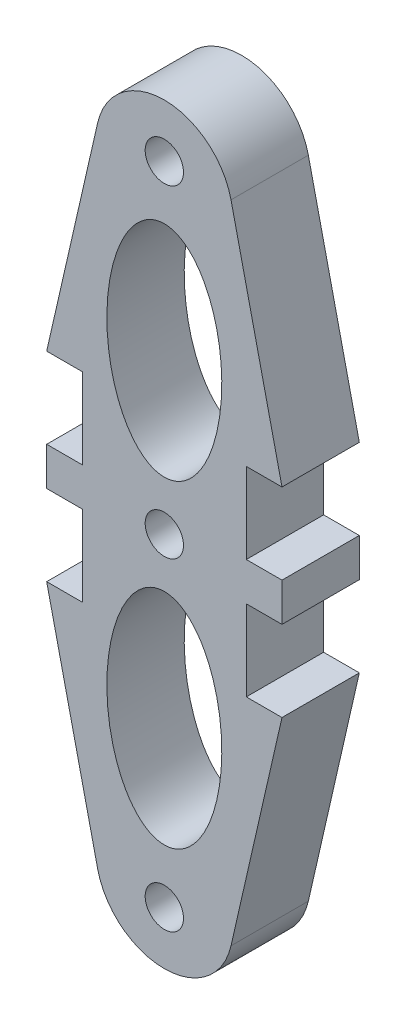
SolidWorks part; units mm, degrees
material "Acrylic (Medium-high impact)"
ref_plane "Front Plane" through (0, 0, 0) normal (0, 0, 1) x (1, 0, 0)
ref_plane "Top Plane" through (0, 0, 0) normal (0, 1, 0) x (1, 0, 0)
ref_plane "Right Plane" through (0, 0, 0) normal (1, 0, 0) x (0, 0, -1)
sketch "Sketch1" plane through (0, 0, 0) normal (0, 0, 1) x (1, 0, 0)
  line L0 (-213.0416, 464.8524) -> (49786.9584, 464.8524) construction
  line L1 (781.4592, 464.8524) -> (778.7592, 464.8524)
  line L2 (781.4592, 464.8524) -> (781.4592, 470.9524)
  line L3 (781.4592, 470.9524) -> (778.7592, 470.9524)
  line L4 (787.6592, -515.9255) -> (787.6592, 49484.0745) construction
  line L5 (-215.2216, 463.4024) -> (49784.7784, 463.4024) construction
  line L6 (793.8592, 470.9524) -> (793.8592, 487.8374) construction
  line L7 (-217.5077, 461.9524) -> (49782.4923, 461.9524) construction
  line L8 (786.2092, -537.0976) -> (786.2092, 49462.9024) construction
  line L9 (789.1092, -536.5976) -> (789.1092, 49463.4024) construction
  line L10 (793.8592, 464.8524) -> (796.5592, 464.8524)
  line L11 (781.4592, 470.9524) -> (793.8592, 470.9524) construction
  line L12 (793.8592, 470.9524) -> (796.5592, 470.9524)
  line L13 (793.8592, 464.8524) -> (793.8592, 470.9524)
  line L14 (778.7592, 464.8524) -> (778.7592, 461.9524)
  line L15 (796.5592, 464.8524) -> (796.5592, 461.9524)
  line L16 (786.2092, 487.8374) -> (782.615, 487.8374) construction
  line L17 (781.4592, 461.9524) -> (778.7592, 461.9524)
  line L18 (793.8592, 470.9524) -> (793.1379, 470.9192) construction
  line L19 (781.4592, 455.8524) -> (778.7592, 455.8524)
  line L20 (781.4592, 461.9524) -> (781.4592, 455.8524)
  line L21 (793.8592, 461.9524) -> (796.5592, 461.9524)
  line L22 (793.8592, 461.9524) -> (793.8592, 455.8524)
  line L23 (793.8592, 455.8524) -> (796.5592, 455.8524)
  line L24 (778.7592, 470.9524) -> (782.615, 487.8374)
  line L25 (792.7033, 487.8374) -> (796.5592, 470.9524)
  line L26 (792.7033, 438.9674) -> (796.5592, 455.8524)
  line L27 (789.1092, 438.9674) -> (792.7033, 438.9674) construction
  line L28 (786.2092, 438.9674) -> (782.615, 438.9674) construction
  line L29 (778.7592, 455.8524) -> (782.615, 438.9674)
  line L35 (789.1092, 487.8374) -> (792.7033, 487.8374) construction
  arc A0 (782.615, 487.8374) -> (792.7033, 487.8374) centre (787.6592, 486.6855) cw
  arc A1 (782.615, 438.9674) -> (792.7033, 438.9674) centre (787.6592, 440.1192) ccw
  circle A3 centre (787.6592, 487.8374) radius 1.45
  circle A5 centre (787.6592, 438.9674) radius 1.45
  circle A6 centre (787.6592, 463.4024) radius 1.45
  ellipse E0 centre (787.6592, 475.4481) end of major axis (787.6592, 483.7502) minor radius 4.3465
  ellipse E1 centre (787.6592, 451.3566) end of major axis (787.6592, 443.0545) minor radius 4.3465
  point P10 (778.7592, 463.4024)
  point P19 (796.5592, 463.4024)
  dimension "D1" = 2.9
  dimension "D3" = 6.1
  dimension "D10" = 5.174
  dimension "D2" = 2.7
  dimension "D5" = 12.4
  dimension "D6" = 16.6042
  dimension "D7" = 8.693
  dimension "D8" = 2.2937
extrude "Boss-Extrude1" add sketch "Sketch1" along normal blind 5.85 contours L3 A3 A5 region at (782.0555, 467.9024, 0)
